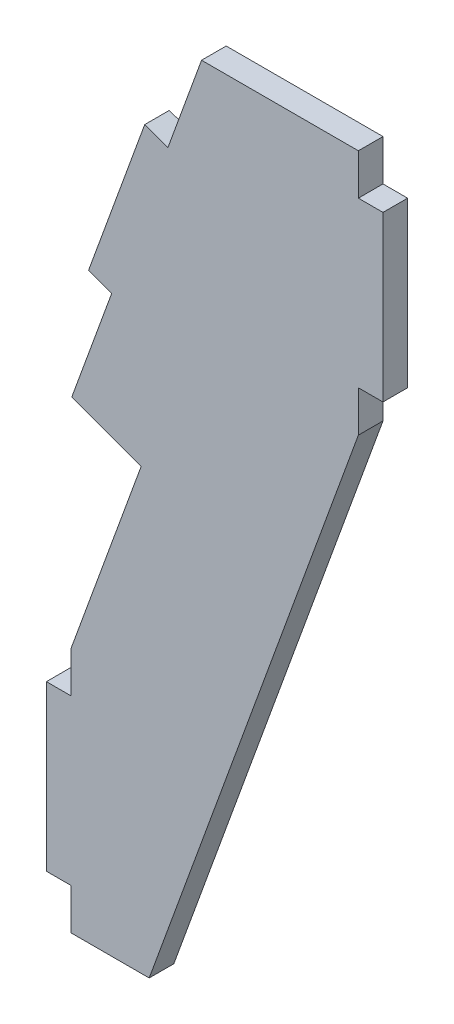
SolidWorks part; units mm, degrees
ref_plane "Front Plane" through (0, 0, 0) normal (0, 0, 1) x (1, 0, 0)
ref_plane "Top Plane" through (0, 0, 0) normal (0, 1, 0) x (1, 0, 0)
ref_plane "Right Plane" through (0, 0, 0) normal (1, 0, 0) x (0, 0, -1)
sketch "Sketch1" plane through (0, 0, 0) normal (0, 0, 1) x (1, 0, 0)
  line L0 (3, -5) -> (12.5221, -5)
  line L1 (38, 95) -> (28.4779, 95)
  line L32 (3, 20) -> (0, 20)
  line L33 (0, 20) -> (0, 0)
  line L34 (0, 0) -> (3, 0)
  line L35 (3, 0) -> (3, -5)
  line L36 (12.5221, -5) -> (38, 65)
  line L37 (38, 65) -> (38, 70)
  line L38 (38, 70) -> (41, 70)
  line L39 (41, 70) -> (41, 90)
  line L40 (41, 90) -> (38, 90)
  line L41 (38, 90) -> (38, 95)
  line L42 (28.4779, 95) -> (18.3909, 67.2862)
  line L43 (18.3909, 67.2862) -> (15.5718, 68.3122)
  line L44 (15.5718, 68.3122) -> (8.7314, 49.5184)
  line L45 (8.7314, 49.5184) -> (11.5505, 48.4923)
  line L46 (11.5505, 48.4923) -> (3, 25)
  line L47 (3, 25) -> (3, 20)
  dimension "D1" = 20
  dimension "D2" = 3
  dimension "D3" = 90
  dimension "D4" = 20
  dimension "D5" = 3
  dimension "D6" = 38
  dimension "D7" = 20
  dimension "D8" = 5
  dimension "D9" = 5
  dimension "D10" = 5
  dimension "D11" = 20
  dimension "D12" = 3
  dimension "D13" = 5
  dimension "D14" = 25
extrude "Boss-Extrude1" add sketch "Sketch1" along normal blind 3
sketch "Sketch2" plane through (0, 0, 0) normal (0, 0, -1) x (-1, 0, 0)
  line L1 (-7.9557, 64.9298) -> (-3.0933, 51.5705)
  line L3 (-7.9557, 64.9298) -> (-5.1366, 65.9559)
  line L5 (-5.1366, 65.9559) -> (-11.977, 84.7497)
  line L7 (-11.977, 84.7497) -> (-14.7961, 83.7237)
  line L8 (-14.7961, 83.7237) -> (-18.9003, 95)
  line L9 (-18.9003, 95) -> (-28.4779, 95)
  line L10 (-28.4779, 95) -> (-18.3909, 67.2862)
  line L11 (-18.3909, 67.2862) -> (-15.5718, 68.3122)
  line L12 (-15.5718, 68.3122) -> (-8.7314, 49.5184)
  line L13 (-3.0933, 51.5705) -> (-8.7314, 49.5184)
  dimension "D1" = 12
  dimension "D2" = 3
  dimension "D3" = 3
  dimension "D4" = 20
  dimension "D5" = 12
extrude "Boss-Extrude2" add sketch "Sketch2" against normal up to vertex (3 mm away) up to point (38, 95, 3)
